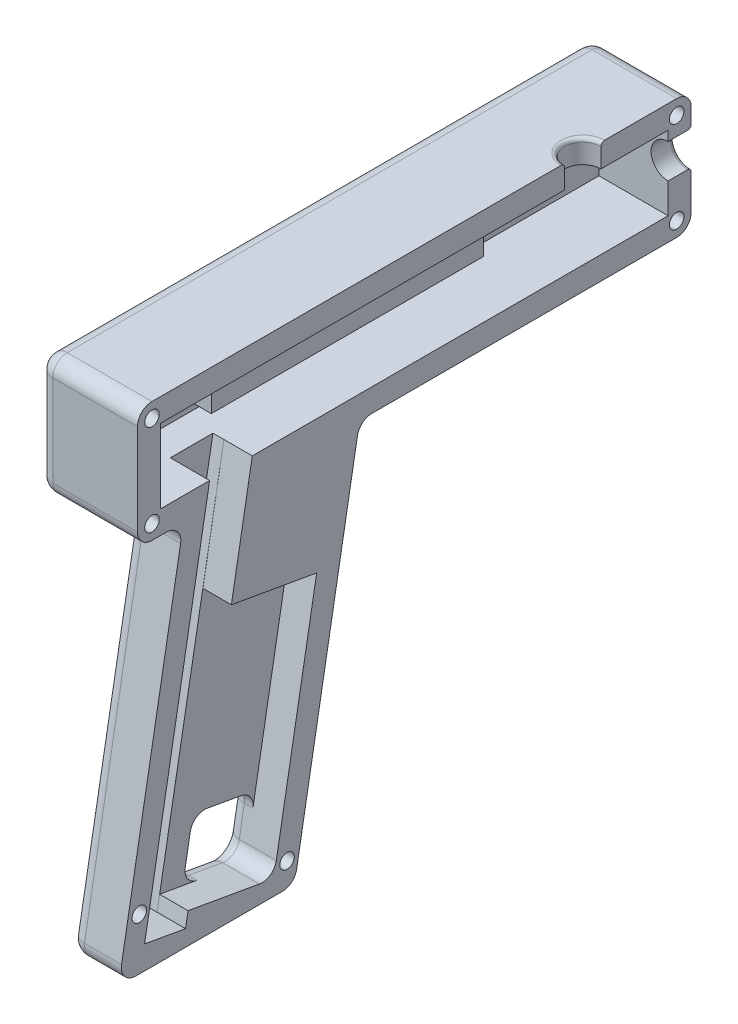
SolidWorks part; units mm, degrees
ref_plane "Front Plane" through (0, 0, 0) normal (0, 0, 1) x (1, 0, 0)
ref_plane "Top Plane" through (0, 0, 0) normal (0, 1, 0) x (1, 0, 0)
ref_plane "Right Plane" through (0, 0, 0) normal (1, 0, 0) x (0, 0, -1)
sketch "Sketch1" plane through (0, 0, 0) normal (0, 0, 1) x (1, 0, 0)
  line L1 (0, 0) -> (27.305, 0)
  line L2 (0, 0) -> (0, 33.1)
  line L3 (0, 33.1) -> (27.305, 33.1)
  line L4 (27.305, 0) -> (27.305, 33.1)
  dimension "D1" = 33.1
  dimension "D2" = 27.305
extrude "Boss-Extrude1" add sketch "Sketch1" against normal blind 152.4
sketch "Sketch2" plane through (27.305, 0, 0) normal (1, 0, 0) x (0, 0, -1)
  line L0 (0, 0) -> (0, 33.1) construction
  line L1 (6.35, 26.75) -> (146.05, 26.75)
  line L2 (6.35, 26.75) -> (6.35, 6.35)
  line L3 (6.35, 6.35) -> (146.05, 6.35)
  line L4 (146.05, 26.75) -> (146.05, 6.35)
  line L5 (152.4, 33.1) -> (0, 33.1) construction
  line L6 (152.4, 0) -> (0, 0) construction
  line L7 (152.4, 0) -> (152.4, 33.1) construction
  point P12 (6.35, 16.55)
  point P13 (0, 16.55)
  dimension "D1" = 6.35
  dimension "D2" = 6.35
  dimension "D3" = 6.35
  dimension "D4" = 6.35
extrude "Cut-Extrude1" cut sketch "Sketch2" against normal blind 19.05
sketch "Sketch4" plane through (0, 33.1, 0) normal (0, 1, 0) x (1, 0, 0)
  line L0 (27.305, 152.4) -> (27.305, 0) construction
  line L2 (27.305, 117.555) -> (27.305, 127.555)
  line L3 (27.305, 152.4) -> (0, 152.4) construction
  arc A2 (27.305, 117.555) -> (27.305, 127.555) centre (27.305, 122.555) cw
  dimension "D1" = 29.845
sketch "Sketch5" plane through (8.255, 0, 0) normal (1, 0, 0) x (0, 0, -1)
  line L0 (33.02, 17.4) -> (107.95, 17.4)
  line L1 (33.02, 23.75) -> (107.95, 23.75)
  line L2 (33.02, 23.75) -> (33.02, 9.35)
  line L3 (33.02, 9.35) -> (107.95, 9.35)
  line L4 (107.95, 23.75) -> (107.95, 9.35)
  line L9 (33.02, 15.7) -> (107.95, 15.7)
  line L10 (6.35, 6.35) -> (146.05, 6.35) construction
  line L11 (146.05, 6.35) -> (146.05, 26.75) construction
  line M13 (146.05, 6.35) -> (146.05, 26.75)
  dimension "D1" = 1.7
  dimension "D2" = 6.35
  dimension "D3" = 6.35
  dimension "D4" = 3
  dimension "D5" = 38.1
  dimension "D6" = 74.93
extrude "PCB Slot" add sketch "Sketch5" along normal blind 6.35 contours L1 L2 L0 M13 | L9 L2 L3 M13 region at (8.255, 20.575, -70.485) region at (8.255, 12.525, -70.485)
sketch "Sketch8" plane through (27.305, 0, 25.4) normal (1, 0, 0) x (0, 0, -1)
  line L0 (38.1, 0) -> (20.1852, -101.6)
  line L1 (20.1852, -101.6) -> (68.621, -101.6)
  line L2 (68.621, -101.6) -> (86.5358, 0)
  line L4 (38.1, 0) -> (86.5358, 0)
  dimension "D1" = 12.7
  dimension "D3" = 47.7
extrude "Butt" add sketch "Sketch8" against normal blind 14.175
sketch "Sketch9" plane through (27.305, 0, 25.4) normal (1, 0, 0) x (0, 0, -1)
  line L7 (68.621, -101.6) -> (86.5358, 0) construction
  line L8 (51.2564, -26.2652) -> (74.7269, -30.4036)
  line L9 (28.0575, -91.2236) -> (62.9188, -97.3706)
  line L10 (74.7269, -30.4036) -> (62.9188, -97.3706)
  line L12 (31.75, 6.35) -> (171.45, 6.35) construction
  line L13 (45.2623, 6.35) -> (57.0073, 6.35)
  line L14 (57.0073, 6.35) -> (51.2564, -26.2652)
  line L15 (45.2623, 6.35) -> (28.0575, -91.2236)
  dimension "D3" = 68
  dimension "D4" = 3.175
extrude "BatteryPack" cut sketch "Sketch9" against normal blind 7.825
sketch "Sketch10" plane through (19.48, 0, 0) normal (1, 0, 0) x (0, 0, -1)
  line L0 (37.5188, -97.3706) -> (20.2847, -94.3317)
  line L1 (37.5188, -97.3706) -> (40.2972, -81.6136)
  line L2 (20.2847, -94.3317) -> (23.0631, -78.5748)
  line L3 (40.2972, -81.6136) -> (23.0631, -78.5748)
  line L4 (2.6575, -91.2236) -> (37.5188, -97.3706) construction
  dimension "D1" = 16
  dimension "D2" = 17.5
extrude "BatterySwitch" cut sketch "Sketch10" against normal up to next
sketch "Sketch11" plane through (0, -88.0184, 15.52) normal (0, 0.9848, -0.1736) x (1, 0, 0)
  line L0 (19.48, 18.4579) -> (27.305, 18.4579)
  line L1 (19.48, 18.4579) -> (19.48, 29.8992)
  line L2 (27.305, 18.4579) -> (27.305, 29.8992)
  line L3 (19.48, 29.8992) -> (27.305, 29.8992)
  dimension "D1" = 11.4413
extrude "WireSpace" cut sketch "Sketch11" against normal blind 4
sketch "Sketch12" plane through (19.48, 0, 0) normal (1, 0, 0) x (0, 0, -1)
  line L0 (19.8623, 6.35) -> (31.6073, 6.35)
  line L1 (31.6073, 6.35) -> (13.2303, -97.1496)
  line L2 (13.2303, -97.1496) -> (1.9629, -95.1628)
  line L3 (1.9629, -95.1628) -> (19.8623, 6.35)
extrude "WireRoute" cut sketch "Sketch12" against normal blind 3
fillet "Fillet-Body" radius 4 24 edges at (13.6525, 0, -152.4) (20.2175, 0, -61.1358) (16.305, -78.5748, -23.0631) (16.305, -94.3317, -20.2847) (13.13, -89.4921, -38.908) (13.13, -95.8511, -28.9018) (13.13, -80.0942, -31.6801) (13.13, -86.4533, -21.6739) (20.2175, -97.3706, -37.5188) (16.305, -81.6136, -40.2972) (20.2175, -101.6, -43.221) (13.13, -101.6, -19.0031) (20.2175, -101.6, 5.2148) (0, 16.55, -152.4) (0, 0, -76.2) (13.13, -50.8, -52.1784) (13.13, -50.8, -3.7426) (13.13, 0, -36.9179) (20.2175, 0, -12.7) (13.6525, 0, 0) (0, 16.55, 0) (13.6525, 33.1, -152.4) (0, 33.1, -76.2) (13.6525, 33.1, 0)
sketch "Sketch13" plane through (27.305, 0, 0) normal (1, 0, 0) x (0, 0, -1)
  line L0 (148.4, 33.1) -> (4, 33.1) construction
  line L1 (0, 4) -> (0, 29.1) construction
  line L2 (7.933, 0) -> (4, 0) construction
  line L3 (152.4, 4) -> (152.4, 29.1) construction
  line L8 (49.3269, -30.4036) -> (25.8564, -26.2652) construction
  line L9 (43.8039, -98.2946) -> (60.553, -3.3054) construction
  line L10 (11.8722, -4.6946) -> (-4.387, -96.9054) construction
  circle A0 centre (4, 29.1) radius 2
  circle A1 centre (148.4, 29.1) radius 2
  circle A2 centre (148.4, 4) radius 2
  circle A3 centre (4, 4) radius 2
  circle A5 centre (0.5231, -87.3425) radius 2
  circle A6 centre (41.1665, -94.9675) radius 2
  dimension "D1" = 4
  dimension "D5" = 64.5486
  dimension "D2" = 4
  dimension "D3" = 4
  dimension "D4" = 4
  dimension "D6" = 65
  dimension "D7" = 3.175
  dimension "D8" = 3.175
extrude "PressFit" cut sketch "Sketch13" against normal blind 5
extrude "HitLED" cut sketch "Sketch4" against normal up to next
sketch "Sketch15" plane through (0, 0, -146.05) normal (0, 0, 1) x (1, 0, 0)
  line L0 (27.305, 6.35) -> (27.305, 26.75) construction
  line L1 (27.305, 24.05) -> (27.305, 14.65)
  arc A0 (27.305, 14.65) -> (27.305, 24.05) centre (27.305, 19.35) cw
  dimension "D1" = 13
extrude "IRLED" cut sketch "Sketch15" against normal up to next
fillet "Fillet-LED's" radius 1 2 edges at (22.605, 19.35, -152.4) (22.305, 33.1, -122.555)
